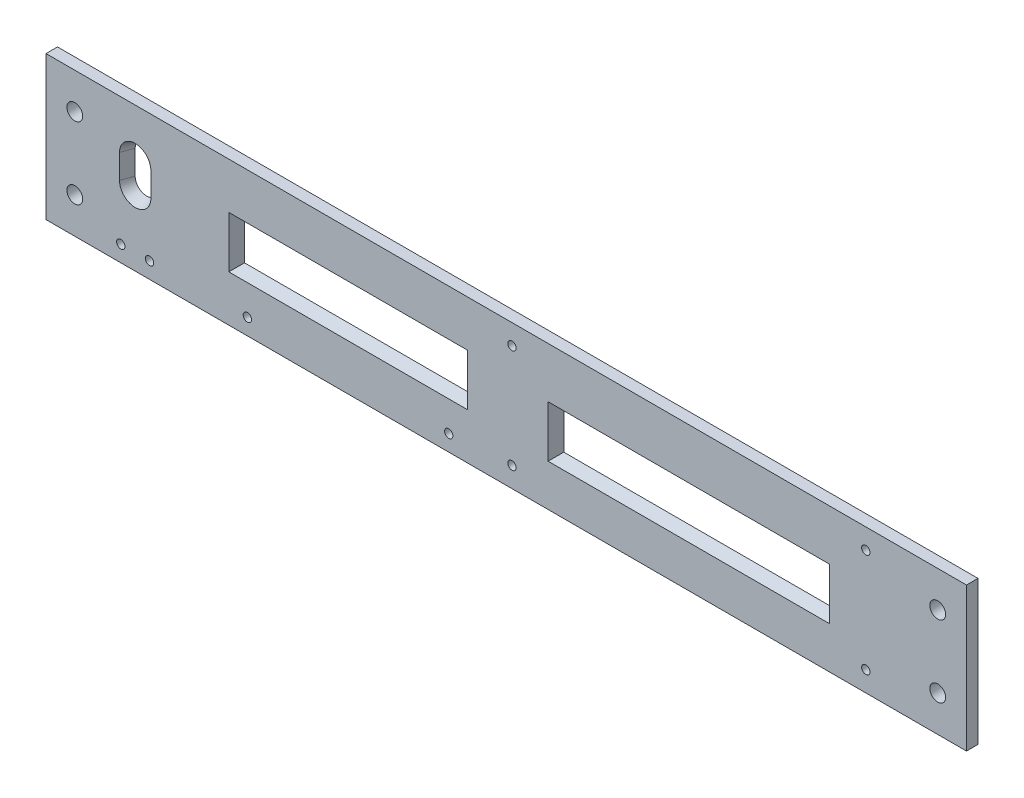
SolidWorks part; units mm, degrees
material "PLA"
ref_plane "Front Plane" through (0, 0, 0) normal (0, 0, 1) x (1, 0, 0)
ref_plane "Top Plane" through (0, 0, 0) normal (0, 1, 0) x (1, 0, 0)
ref_plane "Right Plane" through (0, 0, 0) normal (1, 0, 0) x (0, 0, -1)
sketch "Sketch1" plane through (0, 0, 0) normal (0, 0, 1) x (1, 0, 0)
  line L1 (0, 0) -> (320, 0)
  line L2 (0, 0) -> (0, 50)
  line L3 (0, 50) -> (320, 50)
  line L4 (320, 0) -> (320, 50)
  dimension "D1" = 320
  dimension "D2" = 50
extrude "Boss-Extrude1" add sketch "Sketch1" along normal blind 4
sketch "Sketch2" plane through (0, 0, 4) normal (0, 0, 1) x (1, 0, 0)
  line L0 (0, 37.5) -> (10, 37.5) construction
  line L1 (0, 50) -> (0, 0) construction
  line L2 (10, 37.5) -> (310, 37.5) construction
  line L3 (310, 37.5) -> (320, 37.5) construction
  line L4 (320, 0) -> (320, 50) construction
  line L5 (320, 50) -> (0, 50) construction
  point P11 (10, 37.5)
  point P12 (310, 37.5)
  dimension "D1" = 12.5
  dimension "D2" = 10
hole_wizard "M5 Clearance Hole1" positions "Sketch2" profile "Sketch4" hole size "M5" standard "ANSI Metric"
sketch "Sketch4" plane through (310, 37.5, 4) normal (1, 0, 0) x (0, -1, 0)
  line L0 (0, 0) -> (0, 15.6524)
  line L1 (0, 15.6524) -> (2.75, 14)
  line L2 (2.75, 14) -> (2.75, 0)
  line L5 (2.75, 0) -> (0, 0)
  line L10 (0, 15.6524) -> (-2.75, 14) construction
  line L11 (0, -6.35) -> (0, 107.95) construction
  dimension "Hole Dia." = 5.5
  dimension "Hole Depth" = 14
  dimension "Drill Angle" = 118
pattern_linear "LPattern1" count 2 spacing 25 along (0, -1, 0) of "M5 Clearance Hole1"
sketch "Sketch5" plane through (0, 0, 4) normal (0, 0, 1) x (1, 0, 0)
  line L1 (65, 32.5) -> (145, 32.5)
  line L2 (65, 32.5) -> (65, 17.5)
  line L3 (65, 17.5) -> (145, 17.5)
  line L4 (145, 32.5) -> (145, 17.5)
  line L5 (105, 32.5) -> (105, 17.5) construction
  line L6 (0, 50) -> (0, 0) construction
  line L7 (0, 25) -> (65, 25) construction
  dimension "D1" = 80
  dimension "D2" = 15
  dimension "D4" = 105
extrude "Cut-Extrude1" cut sketch "Sketch5" against normal through all
sketch "Sketch6" plane through (0, 0, 4) normal (0, 0, 1) x (1, 0, 0)
  line L0 (31, 24.6) -> (31, 33) construction
  line L1 (27, 24.6) -> (27, 33)
  line L2 (35, 24.6) -> (35, 33)
  line L3 (0, 50) -> (0, 0) construction
  line L4 (320, 50) -> (0, 50) construction
  arc A0 (27, 24.6) -> (35, 24.6) centre (31, 24.6) ccw
  arc A1 (35, 33) -> (27, 33) centre (31, 33) ccw
  point P2 (31, 28.8)
  dimension "D1" = 8
  dimension "D2" = 8.4
  dimension "D3" = 31
  dimension "D4" = 17
extrude "Cut-Extrude3" cut sketch "Sketch6" against normal through all
sketch "Sketch9" plane through (0, 0, 4) normal (0, 0, 1) x (1, 0, 0)
  line L0 (271, 23.5) -> (320, 23.5) construction
  line L1 (271, 31) -> (176, 31)
  line L2 (271, 31) -> (271, 16)
  line L3 (271, 16) -> (176, 16)
  line L4 (176, 31) -> (176, 16)
  line L6 (320, 0) -> (320, 50) construction
  line L7 (320, 25) -> (271, 25) construction
  dimension "D1" = 49
  dimension "D2" = 95
  dimension "D3" = 15
  dimension "D4" = 1.5
extrude "Cut-Extrude4" cut sketch "Sketch9" against normal through all
sketch "Sketch7" plane through (0, 0, 4) normal (0, 0, 1) x (1, 0, 0)
  line L0 (31, 20.6) -> (31, 5.6) construction
  line L1 (31, 5.6) -> (26, 5.6) construction
  line L2 (31, 5.6) -> (36, 5.6) construction
  line L3 (105, 17.5) -> (105, 5.6) construction
  line L4 (65, 17.5) -> (145, 17.5) construction
  line L5 (105, 5.6) -> (70, 5.6) construction
  line L7 (105, 5.6) -> (140, 5.6) construction
  line L8 (176, 23.5) -> (271, 23.5) construction
  line L9 (176, 31) -> (176, 16) construction
  line L10 (271, 16) -> (271, 31) construction
  line L12 (223.5, 23.5) -> (223.5, 25) construction
  line L15 (162, 7) -> (285, 7) construction
  line L16 (162, 7) -> (162, 43) construction
  line L17 (162, 43) -> (285, 43) construction
  line L18 (285, 7) -> (285, 43) construction
  line L19 (162, 7) -> (285, 43) construction
  line L20 (162, 43) -> (285, 7) construction
  arc A0 (27, 24.6) -> (35, 24.6) centre (31, 24.6) ccw construction
  point P6 (26, 5.6)
  point P7 (36, 5.6)
  point P23 (70, 5.6)
  point P26 (140, 5.6)
  point P275 (162, 43)
  point P278 (162, 7)
  point P281 (285, 7)
  point P284 (285, 43)
  dimension "D1" = 10
  dimension "D2" = 15
  dimension "D3" = 70
  dimension "D4" = 123
  dimension "D5" = 36
  dimension "D6" = 1.5
hole_wizard "M2.5 Clearance Hole1" positions "Sketch7" profile "Sketch8" hole size "M2.5" standard "ANSI Metric" end condition through all
sketch "Sketch8" plane through (285, 43, 4) normal (1, 0, 0) x (0, -1, 0)
  line L0 (0, 0) -> (0, 4)
  line L1 (0, 4) -> (1.45, 4)
  line L2 (1.45, 4) -> (1.45, 0)
  line L5 (1.45, 0) -> (0, 0)
  line L11 (0, -6.35) -> (0, 107.95) construction
  dimension "Thru Hole Dia." = 2.9
  dimension "Thru Hole Depth" = 4
draft "Draft1" type of draft neutral plane draft angle 20 faces to draft 12 face at (223.5, 16, 2) face at (271, 23.5, 2) face at (223.5, 31, 2) face at (176, 23.5, 2) face at (145, 25, 2) face at (105, 32.5, 2) face at (65, 25, 2) face at (105, 17.5, 2) face at (35, 28.8, 2) face at (31, 35, 2) face at (27, 28.8, 2) face at (31, 22.6, 2) neutral plane through (0, 0, 0) neutral plane normal (0, 0, -1) reverse direction yes parameters "D1"=20
